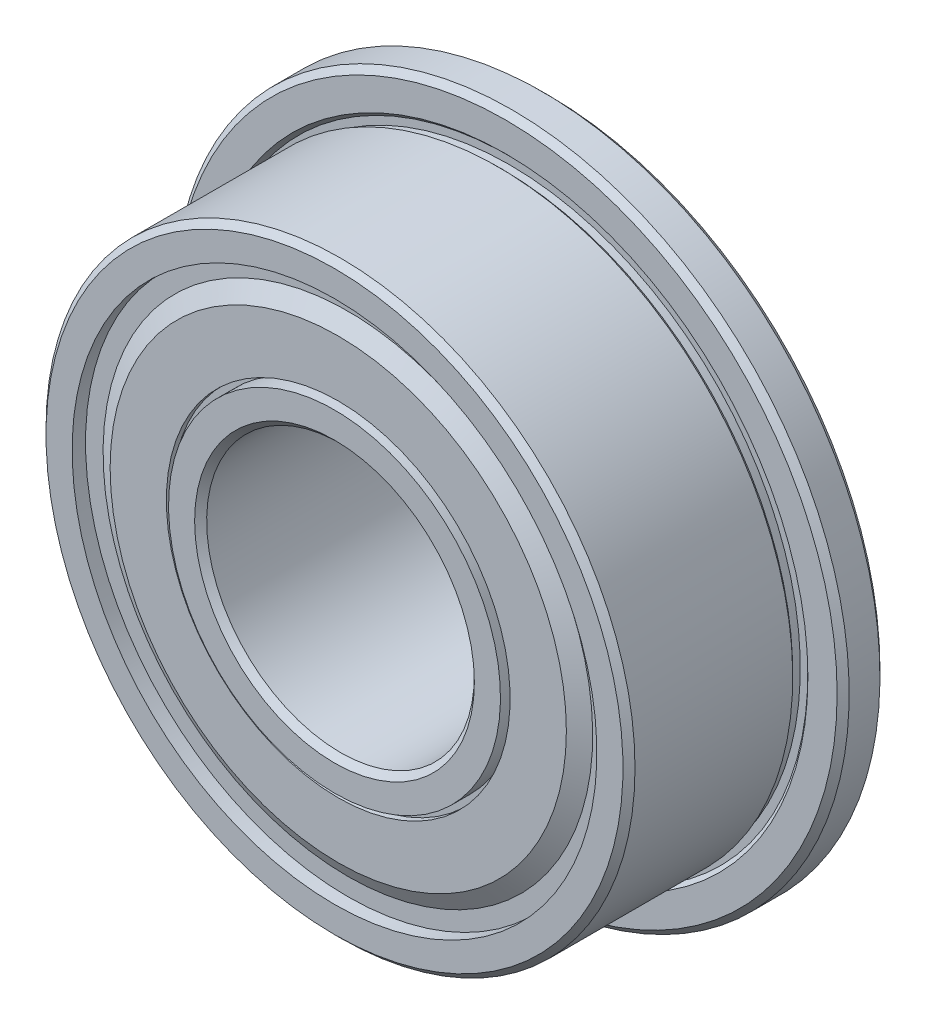
SolidWorks part; units mm, degrees
ref_plane "Front Plane" through (0, 0, 0) normal (0, 0, 1) x (1, 0, 0)
ref_plane "Top Plane" through (0, 0, 0) normal (0, 1, 0) x (1, 0, 0)
ref_plane "Right Plane" through (0, 0, 0) normal (1, 0, 0) x (0, 0, -1)
sketch "Sketch1" plane through (0, 0, 0) normal (1, 0, 0) x (0, 0, -1)
  line L0 (0, 5.5) -> (0, -5.5) construction
  line L1 (-2, 5.5) -> (2, 5.5) construction
  line L2 (0, 0) -> (2, 0) construction
  line L3 (2, 6.3) -> (2, -6.3) construction
  line L4 (2, -6.3) -> (1.2, -6.3) construction
  line L5 (2, 2.5) -> (0, 2.5) construction
  line L6 (2, 2.5) -> (2, -2.5) construction
  dimension "OD" = 11
  dimension "Width" = 4
  dimension "Flange Dia." = 12.6
  dimension "Flange Thickness" = 0.8
  dimension "ID" = 5
sketch "Sketch2" plane through (0, 0, 0) normal (1, 0, 0) x (0, 0, -1)
  line L0 (2, 6.3) -> (1.2, 6.3)
  line L1 (1.2, 6.3) -> (1.2, 5.6414)
  line L2 (1.0586, 5.5) -> (-2, 5.5)
  line L3 (-2, 5.5) -> (-2, 4.6)
  line L4 (-2, 4.6) -> (-0.45, 4.6)
  line L5 (2, 6.3) -> (2, -6.3) construction
  line L6 (2, 4.6) -> (2, 6.3)
  line L7 (2, 2.5) -> (-2, 2.5)
  line L8 (-2, 2.5) -> (-2, 3.4)
  line L9 (-2, 3.4) -> (-0.45, 3.4)
  line L10 (2, 3.4) -> (2, 2.5)
  line L11 (0, 5.5) -> (0, 2.5) construction
  line L12 (-0.75, 4) -> (0.75, 4) construction
  line L13 (0.45, 4.6) -> (2, 4.6)
  line L14 (0.45, 3.4) -> (2, 3.4)
  line L15 (1.2, 5.6414) -> (1.2707, 5.5707)
  line L16 (1.2707, 5.5707) -> (1.2707, 5.4293)
  line L17 (1.2707, 5.4293) -> (1.1293, 5.4293)
  line L18 (1.1293, 5.4293) -> (1.0586, 5.5)
  line L19 (1.2, 5.5) -> (1.2707, 5.4293) construction
  line L20 (1.2707, 5.5707) -> (1.1293, 5.4293) construction
  line L21 (1.0586, 5.5) -> (1.2, 5.5) construction
  line L22 (1.2, 5.5) -> (1.2, 5.6414) construction
  circle A0 centre (0, 4) radius 0.75 construction
  arc A1 (-0.45, 4.6) -> (0.45, 4.6) centre (0, 4) cw
  arc A2 (-0.45, 3.4) -> (0.45, 3.4) centre (0, 4) ccw
  dimension "D1" = 3
  dimension "Ball Dia." = 1.5
  dimension "D2" = 135
  dimension "D3" = 0.2
  dimension "D4" = 1.2
  dimension "Race Thikness" = 0.9
revolve "Revolve1" add sketch "Sketch2" angle 360 about L2
fillet "Fillet1" radius 0.1125 3 edges at (0, -6.3, -2) (0, -6.3, -1.2) (0, -5.5, 2) profile chamfer
sketch "Sketch3" plane through (0, 0, 0) normal (0, 0, 1) x (1, 0, 0)
  line L0 (-2.5, 0) -> (2.5, 0) construction
  line L1 (-5.5, 0) -> (5.5, 0) construction
  point P5 (0, 0)
  dimension "ID2" = 5
  dimension "OD2" = 11
fillet "Fillet2" radius 0.1125 2 edges at (0, -2.5, -2) (0, -2.5, 2) profile chamfer
sketch "Sketch7" plane through (0, 0, 0) normal (0, 0, 1) x (1, 0, 0)
  line L0 (0, 4.75) -> (0, 3.25)
  line L1 (0, 6.3) -> (0, -6.3) construction
  line L2 (-0.9067, 4.75) -> (0, 0) construction
  line L3 (0, 0) -> (0.9067, 4.75) construction
  line L4 (0.9067, 4.75) -> (-0.9067, 4.75) construction
  circle A0 centre (0, 4) radius 0.75 construction
  circle A1 centre (0, 0) radius 4.75 construction
  circle A2 centre (0, 0) radius 3.25 construction
  arc A4 (0, 4.75) -> (0, 3.25) centre (0, 4) ccw
  dimension "D1" = 21.614
revolve "Revolve3" add sketch "Sketch7" angle 360 about L0
pattern_circular "CirPattern3" count 13 over 360 about axis through (0, 0, 0) along (0, 0, -1) of bodies 107
sketch "Sketch8" plane through (0, 0, 0) normal (1, 0, 0) x (0, 0, -1)
  line L1 (-2, 4.6) -> (-1.64, 4.6)
  line L2 (-2, 4.6) -> (-2, 4.9)
  line L3 (-2, 4.9) -> (-1.64, 4.9)
  line L4 (-1.64, 4.6) -> (-1.64, 4.9)
  line L5 (2, 4.6) -> (1.64, 4.6)
  line L6 (2, 4.6) -> (2, 4.9)
  line L7 (2, 4.9) -> (1.64, 4.9)
  line L8 (1.64, 4.6) -> (1.64, 4.9)
  line L9 (2, 3.4) -> (1.64, 3.4)
  line L10 (2, 3.4) -> (2, 3.1)
  line L11 (2, 3.1) -> (1.64, 3.1)
  line L12 (1.64, 3.4) -> (1.64, 3.1)
  line L13 (-2, 3.4) -> (-1.64, 3.4)
  line L14 (-2, 3.4) -> (-2, 3.1)
  line L15 (-2, 3.1) -> (-1.64, 3.1)
  line L16 (-1.64, 3.4) -> (-1.64, 3.1)
  dimension "D1" = 0.3
  dimension "D2" = 0.36
revolve "Cut-Revolve1" cut sketch "Sketch8" angle 360 about L2
sketch "Sketch9" plane through (0, 0, 0) normal (1, 0, 0) x (0, 0, -1)
  line L0 (-1.64, 4.9) -> (-1.64, 4.5429)
  line L1 (-1.64, 4.5429) -> (-1.82, 4.2311)
  line L2 (-1.82, 4.2311) -> (-1.82, 3.21)
  line L3 (1.82, 3.21) -> (1.82, 3.1) construction
  line L4 (1.64, 4.9) -> (1.64, 4.5429)
  line L5 (1.64, 4.5429) -> (1.82, 4.2311)
  line L6 (1.82, 4.2311) -> (1.82, 3.21)
  line L7 (2, 3.1) -> (1.64, 3.1) construction
  line L8 (-1.75, 4.9) -> (-1.75, 4.5723)
  line L9 (-1.75, 4.5723) -> (-1.93, 4.2606)
  line L10 (-1.93, 4.2606) -> (-1.93, 3.21)
  line L11 (-1.64, 4.9) -> (-1.75, 4.9)
  line L12 (-1.82, 3.21) -> (-1.93, 3.21)
  line L13 (1.73, 4.9) -> (1.73, 4.567)
  line L14 (1.73, 4.567) -> (1.91, 4.2552)
  line L15 (1.91, 4.2552) -> (1.91, 3.21)
  line L16 (1.64, 4.9) -> (1.73, 4.9)
  line L17 (1.82, 3.21) -> (1.91, 3.21)
  line L18 (-1.64, 4.5429) -> (-1.64, 2.6) construction
  line L19 (1.64, 4.5429) -> (1.64, 4.9) construction
  line L20 (-1.64, 3.1) -> (-2, 3.1) construction
  line L22 (-1.82, 3.21) -> (-1.82, 3.1) construction
  dimension "D2" = 150
  dimension "D1" = 150
  dimension "D5" = 0.36
  dimension "D3" = 0.11
  dimension "D4" = 0.09
  dimension "D6" = 0.3571
revolve "Revolve4" add sketch "Sketch9" angle 360 about L2
equation "\"Ball Dia.@Sketch2\"=\"D1@Sketch2\"*.5"
equation "\"D3@Sketch2\"=\"Flange Thickness@Sketch1\"/4"
equation "\"D1@Fillet1\"=\"Race Thikness@Sketch2\"/8"
equation "\"ID2@Sketch3\" = \"ID@Sketch1\""
equation "\"OD2@Sketch3\" = \"OD@Sketch1\""
equation "\"D1@Fillet2\"=\"Race Thikness@Sketch2\"/8"
equation "\"D1@CirPattern3\"=360/\"D1@Sketch7\"-4"
equation "\"D1@Sketch8\"=\"Race Thikness@Sketch2\"/3"
equation "\"D2@Sketch8\"=\"Race Thikness@Sketch2\"/2.5"
equation "\"D4@Sketch9\"=\"D5@Sketch9\"/4"
equation "\"D1@Sketch9\"=\"D2@Sketch9\""
equation "\"D4@Sketch2\"=\"D1@Sketch2\"*.4"
